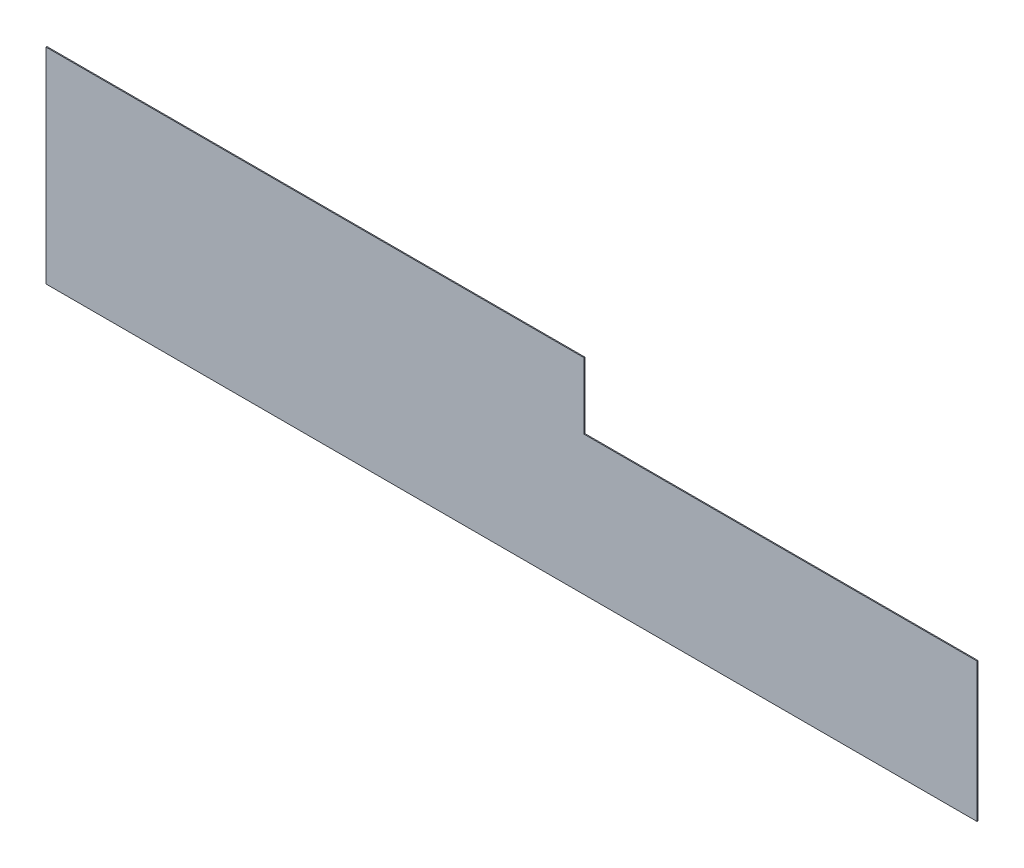
SolidWorks part; units mm, degrees
ref_plane "Ön Düzlem" through (0, 0, 0) normal (0, 0, 1) x (1, 0, 0)
ref_plane "Üst Düzlem" through (0, 0, 0) normal (0, 1, 0) x (1, 0, 0)
ref_plane "Sağ Düzlem" through (0, 0, 0) normal (1, 0, 0) x (0, 0, -1)
sketch "Çizim1" plane through (0, 0, 0) normal (0, 0, 1) x (1, 0, 0)
  line L0 (0, 0) -> (0, 1255)
  line L1 (0, 1255) -> (3290, 1255)
  line L2 (3290, 1255) -> (3290, 850)
  line L3 (3290, 850) -> (5695, 850)
  line L4 (5695, 850) -> (5695, 0)
  line L5 (5695, 0) -> (0, 0)
  dimension "D1" = 3290
  dimension "D2" = 405
  dimension "D3" = 2405
  dimension "D4" = 850
  dimension "D5" = 5695
  dimension "D6" = 1255
base flange "Taban-Flanş1" sketch "Çizim1" thickness 6 reverse thickness direction no parameters "D1"=12
sketch "Büküm-Çizgileri1" [suppressed] plane through (0, 0, 0) normal (0, 1, 0) x (1, 0, 0)
sketch "Sınırlandırma-Kutusu1" [suppressed] plane through (0, 0, 0) normal (0, 1, 0) x (1, 0, 0)
sheet metal parameters "Sac-Levha1" thickness 6 parameters "D1"=12
flat pattern "Düz-Çoğaltma1" [suppressed]
sketch "Büküm-Çizgileri2" plane through (0, 0, 0) normal (0, 1, 0) x (1, 0, 0)
sketch3d "Sınırlandırma-Kutusu2" [suppressed]
  line L0 (0, 0, 0) -> (-5695, 0, 0) construction
  line L1 (0, 1255, 0) -> (-5695, 1255, 0) construction
  line L2 (0, 0, 0) -> (0, 1255, 0) construction
  line L3 (-5695, 0, 0) -> (-5695, 1255, 0) construction
